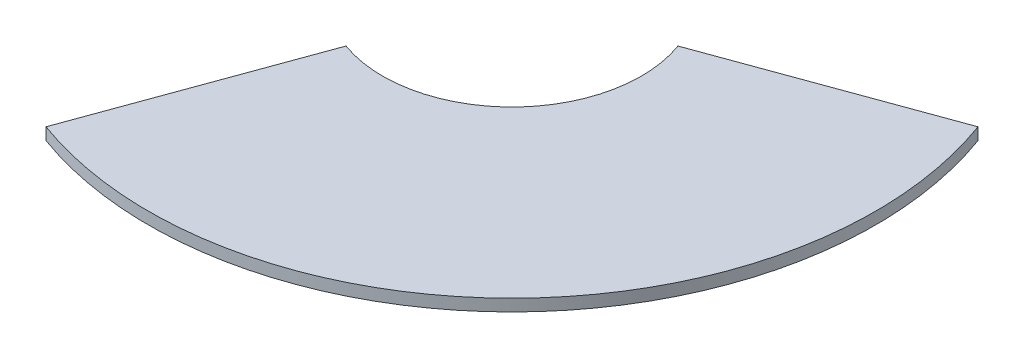
SolidWorks part; units mm, degrees
ref_plane "Front Plane" through (0, 0, 0) normal (0, 0, 1) x (1, 0, 0)
ref_plane "Top Plane" through (0, 0, 0) normal (0, 1, 0) x (1, 0, 0)
ref_plane "Right Plane" through (0, 0, 0) normal (1, 0, 0) x (0, 0, -1)
sketch "Sketch2" plane through (0, 0, 0) normal (0, 1, 0) x (1, 0, 0)
  line L0 (0, 0) -> (-31.2149, -85.7622)
  line L1 (0, 0) -> (85.7622, 31.2149)
  line L2 (0, 0) -> (0, -23.7748) construction
  line L3 (0, 0) -> (25.7561, 0) construction
  circle A0 centre (0, 0) radius 91.2663
  circle A1 centre (0, 0) radius 32.5
  dimension "D1" = 20
  dimension "D2" = 20
extrude "Boss-Extrude2" add sketch "Sketch2" along normal blind 3 contours A1 L0 A0 L1 region at (37.5847, 0, 37.5847)
